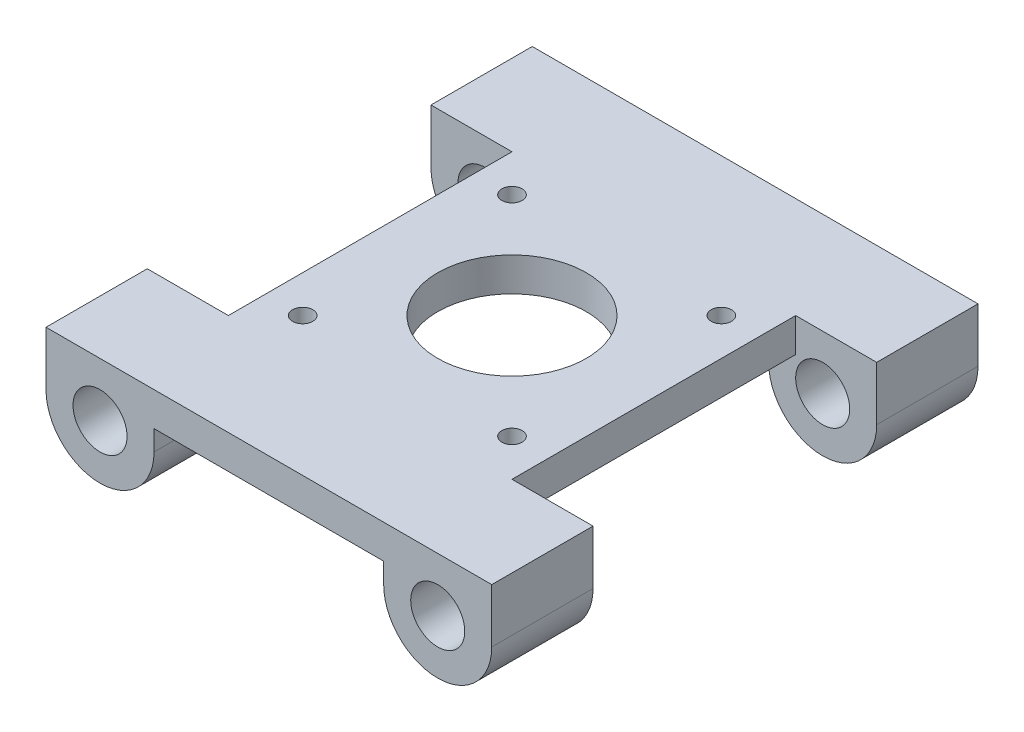
SolidWorks part; units mm, degrees
material "ABS"
ref_plane "Front Plane" through (0, 0, 0) normal (0, 0, 1) x (1, 0, 0)
ref_plane "Top Plane" through (0, 0, 0) normal (0, 1, 0) x (1, 0, 0)
ref_plane "Right Plane" through (0, 0, 0) normal (1, 0, 0) x (0, 0, -1)
sketch "Sketch1" plane through (0, 0, 0) normal (0, 0, 1) x (1, 0, 0)
  line L0 (0, 74.8863) -> (0, -94.3789) construction
  line L1 (33, 0) -> (-33, 0)
  line L2 (-33, 0) -> (-33, -8)
  line L3 (17, -5) -> (-17, -5)
  line L4 (-17, -5) -> (-17, -8)
  line L5 (17, -5) -> (17, -8)
  line L6 (33, 0) -> (33, -8)
  circle A0 centre (-25, -8) radius 4
  arc A1 (-33, -8) -> (-17, -8) centre (-25, -8) ccw
  arc A2 (33, -8) -> (17, -8) centre (25, -8) cw
  circle A3 centre (25, -8) radius 4
  point P16 (0, -5)
  point P17 (0, 0)
  dimension "D1" = 8
  dimension "D5" = 8
  dimension "D2" = 25
  dimension "D3" = 8
  dimension "D4" = 5
extrude "Boss-Extrude1" add sketch "Sketch1" against normal blind 15
sketch "Sketch2" plane through (0, 0, -15) normal (0, 0, -1) x (-1, 0, 0)
  line L0 (21, 0) -> (-21, 0)
  line L1 (-33, 0) -> (33, 0) construction
  line L2 (-21, 0) -> (-21, -5)
  line L3 (-21, -5) -> (21, -5)
  line L4 (17, -5) -> (-17, -5) construction
  line L5 (0, 7.9638) -> (0, -15.9981) construction
  line L6 (21, 0) -> (21, -5)
  point P12 (0, -5)
  point P13 (0, 0)
  dimension "D1" = 21
extrude "Boss-Extrude2" add sketch "Sketch2" along normal blind 42
extrude "Boss-Extrude3" add sketch "Sketch1<2>" against normal blind 15 from vertex starting at point (-21, 0, -57)
sketch "Sketch1<2>" plane through (0, 0, 0) normal (0, 0, 1) x (1, 0, 0) same geometry as "Sketch1"
sketch "Sketch3" plane through (0, 0, 0) normal (0, 1, 0) x (1, 0, 0)
  line L0 (0, -9.6218) -> (0, 80.5515) construction
  line L1 (-21, 36) -> (21, 36) construction
  line L2 (-21, 57) -> (-21, 15) construction
  line L3 (21, 57) -> (21, 15) construction
  circle A0 centre (-15.5, 51.5) radius 1.5
  circle A1 centre (0, 36) radius 11
  circle A2 centre (15.5, 51.5) radius 1.5
  circle A3 centre (15.5, 20.5) radius 1.5
  circle A4 centre (-15.5, 20.5) radius 1.5
  dimension "D1" = 3
  dimension "D4" = 22
  dimension "D2" = 15.5
  dimension "D3" = 15.5
  dimension "D5" = 2
  dimension "D6" = 2
extrude "Cut-Extrude1" cut sketch "Sketch3" against normal through all
equation "\"rod_diameter\"= 8"
equation "\"rod_hole_thickness\"= 4"
equation "\"rod_radius\"= \"rod_diameter\" / 2"
equation "\"platter_diameter\"= 320"
equation "\"platter_radius\"= \"platter_diameter\" / 2"
equation "\"extruder_mount_hole_spacing\"= 75"
equation "\"arm_rod_spacing\"= 40"
equation "\"top_frame_rod_spacing\"= \"arm_rod_spacing\" + 40"
equation "\"motor_level_rod_spacing\"= 15"
equation "\"linear_bearing_diameter\"= 15"
equation "\"z_rod_spacing\"= 75"
equation "\"platter_rod_spacing\"= 50"
equation "\"rod_nut_thickness\"= 6.5"
equation "\"rod_nut_inscribed_diameter\"= 13"
equation "\"z_height\"= 400"
equation "\"D1@Sketch1\"=\"rod_diameter\""
equation "\"D2@Sketch1\"=\"platter_rod_spacing\"/2"
equation "\"D3@Sketch1\"=\"rod_radius\"+\"rod_hole_thickness\""
equation "\"D5@Sketch1\"=\"rod_radius\"+\"rod_hole_thickness\""
equation "\"D2@Sketch3\"=31/2"
